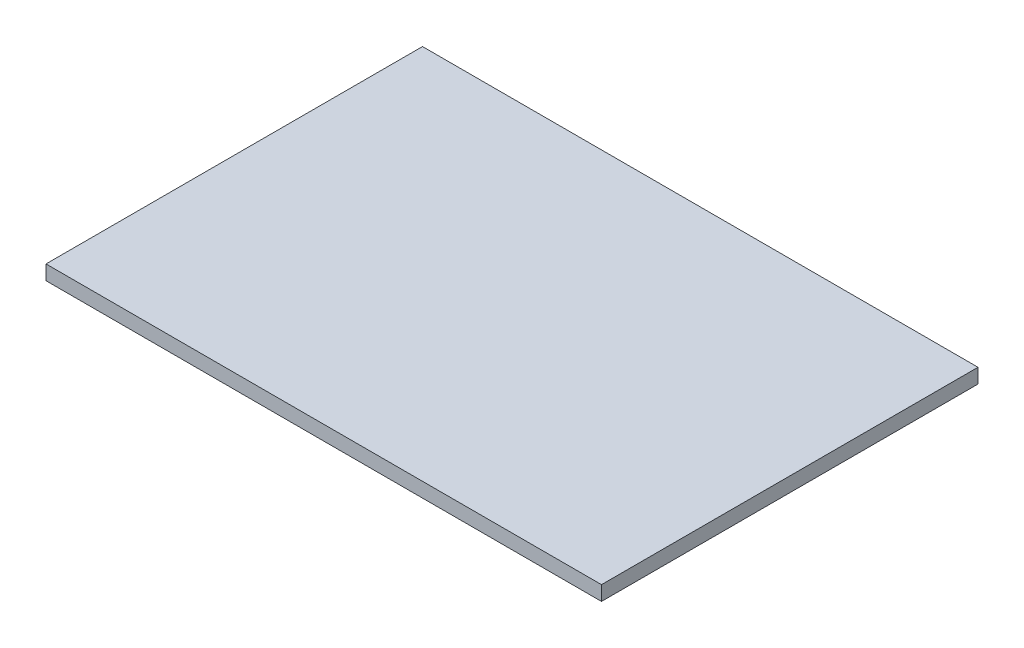
SolidWorks part; units mm, degrees
ref_plane "Front Plane" through (0, 0, 0) normal (0, 0, 1) x (1, 0, 0)
ref_plane "Top Plane" through (0, 0, 0) normal (0, 1, 0) x (1, 0, 0)
ref_plane "Right Plane" through (0, 0, 0) normal (1, 0, 0) x (0, 0, -1)
sketch "Sketch1" plane through (0, 0, 0) normal (0, 1, 0) x (1, 0, 0)
  line L1 (-45, 30.5) -> (45, 30.5)
  line L2 (-45, 30.5) -> (-45, -30.5)
  line L3 (-45, -30.5) -> (45, -30.5)
  line L4 (45, 30.5) -> (45, -30.5)
  line L5 (-45, 30.5) -> (45, -30.5) construction
  line L6 (-45, -30.5) -> (45, 30.5) construction
  point P0 (0, 0)
  dimension "D1" = 61
  dimension "D2" = 90
extrude "Boss-Extrude1" add sketch "Sketch1" along normal mid plane 2.36
sketch "Sketch2" plane through (0, -1.18, 0) normal (0, -1, 0) x (1, 0, 0)
  line L0 (-9, -1.05) -> (-9, -11.25) construction
  line L1 (45, 30.5) -> (-45, 30.5)
  line L2 (45, 30.5) -> (45, -30.5)
  line L3 (45, -30.5) -> (-45, -30.5)
  line L4 (-45, 30.5) -> (-45, -30.5)
  line L5 (-9, 0.05) -> (-32, 0.05)
  line L6 (-9, 0.05) -> (-9, 11.25)
  line L7 (-9, 11.25) -> (-32, 11.25)
  line L8 (-32, 0.05) -> (-32, 11.25)
  line L9 (-32, -0.05) -> (-9, -0.05)
  line L10 (-32, -0.05) -> (-32, -11.25)
  line L11 (-32, -11.25) -> (-9, -11.25)
  line L12 (-9, -0.05) -> (-9, -11.25)
  line L13 (11.4572, 30.5) -> (11.4572, -30.5)
  line L134 (11.4572, 38.6) -> (11.4572, -38.6) construction
  line L135 (-43.5487, 0.655) -> (-43.5487, 0.305)
  line L136 (-43.5487, 3.195) -> (-43.1487, 3.195)
  line L137 (-0.0946, -23.8068) -> (6.2919, -23.8068)
  line L138 (-0.0946, -23.8068) -> (-0.0946, -30.1932)
  line L139 (-0.0946, -30.1932) -> (6.2919, -30.1932)
  line L140 (6.2919, -23.8068) -> (6.2919, -30.1932)
  line L141 (-43.5487, 3.195) -> (-43.5487, 2.845)
  line L142 (-43.5487, 2.845) -> (-43.1487, 2.845)
  line L143 (-43.1487, 3.195) -> (-43.1487, 2.845)
  line L144 (-43.5487, 0.655) -> (-43.1487, 0.655)
  line L145 (-43.1487, 0.655) -> (-43.1487, 0.305)
  line L146 (-43.5487, 0.305) -> (-43.1487, 0.305)
  line L147 (-43.5487, -1.885) -> (-43.5487, -2.235)
  line L148 (-43.5487, -1.885) -> (-43.1487, -1.885)
  line L149 (-43.1487, -1.885) -> (-43.1487, -2.235)
  line L150 (-43.5487, -2.235) -> (-43.1487, -2.235)
  line L151 (-43.5487, -4.425) -> (-43.5487, -4.775)
  line L152 (-43.5487, -4.425) -> (-43.1487, -4.425)
  line L153 (-43.1487, -4.425) -> (-43.1487, -4.775)
  line L154 (-43.5487, -4.775) -> (-43.1487, -4.775)
  line L155 (-43.5487, -6.965) -> (-43.5487, -7.315)
  line L156 (-43.5487, -6.965) -> (-43.1487, -6.965)
  line L157 (-43.1487, -6.965) -> (-43.1487, -7.315)
  line L158 (-43.5487, -7.315) -> (-43.1487, -7.315)
  line L159 (-43.5487, -9.505) -> (-43.5487, -9.855)
  line L160 (-43.5487, -9.505) -> (-43.1487, -9.505)
  line L161 (-43.1487, -9.505) -> (-43.1487, -9.855)
  line L162 (-43.5487, -9.855) -> (-43.1487, -9.855)
  line L163 (-43.5487, 3.195) -> (-43.5487, 0.655) construction
  line L164 (-6.85, 13.02) -> (-6.85, 12.38)
  line L165 (-6.85, 15.56) -> (-6.21, 15.56)
  line L166 (-6.85, 15.56) -> (-6.85, 14.92)
  line L167 (-6.85, 14.92) -> (-6.21, 14.92)
  line L168 (-6.21, 15.56) -> (-6.21, 14.92)
  line L169 (-6.85, 13.02) -> (-6.21, 13.02)
  line L170 (-6.21, 13.02) -> (-6.21, 12.38)
  line L171 (-6.85, 12.38) -> (-6.21, 12.38)
  line L172 (-6.85, 10.48) -> (-6.85, 9.84)
  line L173 (-6.85, 10.48) -> (-6.21, 10.48)
  line L174 (-6.21, 10.48) -> (-6.21, 9.84)
  line L175 (-6.85, 9.84) -> (-6.21, 9.84)
  line L176 (-6.85, 7.94) -> (-6.85, 7.3)
  line L177 (-6.85, 7.94) -> (-6.21, 7.94)
  line L178 (-6.21, 7.94) -> (-6.21, 7.3)
  line L179 (-6.85, 7.3) -> (-6.21, 7.3)
  line L180 (-6.85, 5.4) -> (-6.85, 4.76)
  line L181 (-6.85, 5.4) -> (-6.21, 5.4)
  line L182 (-6.21, 5.4) -> (-6.21, 4.76)
  line L183 (-6.85, 4.76) -> (-6.21, 4.76)
  line L184 (-6.85, 2.86) -> (-6.85, 2.22)
  line L185 (-6.85, 2.86) -> (-6.21, 2.86)
  line L186 (-6.21, 2.86) -> (-6.21, 2.22)
  line L187 (-6.85, 2.22) -> (-6.21, 2.22)
  line L188 (-6.85, 0.32) -> (-6.85, -0.32)
  line L189 (-6.85, 0.32) -> (-6.21, 0.32)
  line L190 (-6.21, 0.32) -> (-6.21, -0.32)
  line L191 (-6.85, -0.32) -> (-6.21, -0.32)
  line L192 (-6.85, -2.22) -> (-6.85, -2.86)
  line L193 (-6.85, -2.22) -> (-6.21, -2.22)
  line L194 (-6.21, -2.22) -> (-6.21, -2.86)
  line L195 (-6.85, -2.86) -> (-6.21, -2.86)
  line L196 (-6.85, -4.76) -> (-6.85, -5.4)
  line L197 (-6.85, -4.76) -> (-6.21, -4.76)
  line L198 (-6.21, -4.76) -> (-6.21, -5.4)
  line L199 (-6.85, -5.4) -> (-6.21, -5.4)
  line L200 (-6.85, -7.3) -> (-6.85, -7.94)
  line L201 (-6.85, -7.3) -> (-6.21, -7.3)
  line L202 (-6.21, -7.3) -> (-6.21, -7.94)
  line L203 (-6.85, -7.94) -> (-6.21, -7.94)
  line L204 (-6.85, -9.84) -> (-6.85, -10.48)
  line L205 (-6.85, -9.84) -> (-6.21, -9.84)
  line L206 (-6.21, -9.84) -> (-6.21, -10.48)
  line L207 (-6.85, -10.48) -> (-6.21, -10.48)
  line L208 (-6.85, -12.38) -> (-6.85, -13.02)
  line L209 (-6.85, -12.38) -> (-6.21, -12.38)
  line L210 (-6.21, -12.38) -> (-6.21, -13.02)
  line L211 (-6.85, -13.02) -> (-6.21, -13.02)
  line L212 (-6.85, -14.92) -> (-6.85, -15.56)
  line L213 (-6.85, -14.92) -> (-6.21, -14.92)
  line L214 (-6.21, -14.92) -> (-6.21, -15.56)
  line L215 (-6.85, -15.56) -> (-6.21, -15.56)
  line L216 (-6.85, -17.46) -> (-6.85, -18.1)
  line L217 (-6.85, -17.46) -> (-6.21, -17.46)
  line L218 (-6.21, -17.46) -> (-6.21, -18.1)
  line L219 (-6.85, -18.1) -> (-6.21, -18.1)
  line L220 (-6.85, -20) -> (-6.85, -20.64)
  line L221 (-6.85, -20) -> (-6.21, -20)
  line L222 (-6.21, -20) -> (-6.21, -20.64)
  line L223 (-6.85, -20.64) -> (-6.21, -20.64)
  line L224 (-6.85, 15.56) -> (-6.85, 13.02) construction
  line L225 (-34.79, 7.94) -> (-34.79, 7.3)
  line L226 (-2.4189, 29.58) -> (-1.6269, 29.58)
  line L227 (-2.4189, 29.58) -> (-2.4189, 28.5)
  line L228 (-2.4189, 28.5) -> (-1.6269, 28.5)
  line L229 (-1.6269, 29.58) -> (-1.6269, 28.5)
  line L230 (-2.4189, 23.82) -> (-1.6269, 23.82)
  line L231 (-2.4189, 23.82) -> (-2.4189, 22.74)
  line L232 (-2.4189, 22.74) -> (-1.6269, 22.74)
  line L233 (-1.6269, 23.82) -> (-1.6269, 22.74)
  line L234 (7.8241, 29.58) -> (8.6161, 29.58)
  line L235 (7.8241, 29.58) -> (7.8241, 28.5)
  line L236 (7.8241, 28.5) -> (8.6161, 28.5)
  line L237 (8.6161, 29.58) -> (8.6161, 28.5)
  line L238 (7.8241, 23.82) -> (8.6161, 23.82)
  line L239 (7.8241, 23.82) -> (7.8241, 22.74)
  line L240 (7.8241, 22.74) -> (8.6161, 22.74)
  line L241 (8.6161, 23.82) -> (8.6161, 22.74)
  line L242 (-0.2134, 29.472) -> (6.4106, 29.472)
  line L243 (-0.2134, 29.472) -> (-0.2134, 22.848)
  line L244 (-0.2134, 22.848) -> (6.4106, 22.848)
  line L245 (6.4106, 29.472) -> (6.4106, 22.848)
  line L246 (-34.79, 10.48) -> (-34.15, 10.48)
  line L247 (-34.79, 10.48) -> (-34.79, 9.84)
  line L248 (-34.79, 9.84) -> (-34.15, 9.84)
  line L249 (-34.15, 10.48) -> (-34.15, 9.84)
  line L250 (-34.79, 7.94) -> (-34.15, 7.94)
  line L251 (-34.15, 7.94) -> (-34.15, 7.3)
  line L252 (-34.79, 7.3) -> (-34.15, 7.3)
  line L253 (-34.79, 5.4) -> (-34.79, 4.76)
  line L254 (-34.79, 5.4) -> (-34.15, 5.4)
  line L255 (-34.15, 5.4) -> (-34.15, 4.76)
  line L256 (-34.79, 4.76) -> (-34.15, 4.76)
  line L257 (-34.79, 2.86) -> (-34.79, 2.22)
  line L258 (-34.79, 2.86) -> (-34.15, 2.86)
  line L259 (-34.15, 2.86) -> (-34.15, 2.22)
  line L260 (-34.79, 2.22) -> (-34.15, 2.22)
  line L261 (-34.79, 0.32) -> (-34.79, -0.32)
  line L262 (-34.79, 0.32) -> (-34.15, 0.32)
  line L263 (-34.15, 0.32) -> (-34.15, -0.32)
  line L264 (-34.79, -0.32) -> (-34.15, -0.32)
  line L265 (-34.79, -2.22) -> (-34.79, -2.86)
  line L266 (-34.79, -2.22) -> (-34.15, -2.22)
  line L267 (-34.15, -2.22) -> (-34.15, -2.86)
  line L268 (-34.79, -2.86) -> (-34.15, -2.86)
  line L269 (-34.79, -4.76) -> (-34.79, -5.4)
  line L270 (-34.79, -4.76) -> (-34.15, -4.76)
  line L271 (-34.15, -4.76) -> (-34.15, -5.4)
  line L272 (-34.79, -5.4) -> (-34.15, -5.4)
  line L273 (-34.79, -7.3) -> (-34.79, -7.94)
  line L274 (-34.79, -7.3) -> (-34.15, -7.3)
  line L275 (-34.15, -7.3) -> (-34.15, -7.94)
  line L276 (-34.79, -7.94) -> (-34.15, -7.94)
  line L277 (-34.79, -9.84) -> (-34.79, -10.48)
  line L278 (-34.79, -9.84) -> (-34.15, -9.84)
  line L279 (-34.15, -9.84) -> (-34.15, -10.48)
  line L280 (-34.79, -10.48) -> (-34.15, -10.48)
  line L281 (-34.79, 10.48) -> (-34.79, 7.94) construction
  line L283 (-24.25, -28.34) -> (-16.75, -28.34)
  line L284 (-24.25, -28.34) -> (-24.25, -33.04)
  line L285 (-36.25, 26.51) -> (-4.75, 26.51)
  line L286 (-36.25, 26.51) -> (-36.25, -31.59)
  line L287 (-36.25, -31.59) -> (-4.75, -31.59)
  line L288 (-4.75, 26.51) -> (-4.75, -31.59)
  line L289 (-24.25, -33.04) -> (-16.75, -33.04)
  line L290 (-16.75, -28.34) -> (-16.75, -33.04)
  circle A0 centre (-13, 5.65) radius 1.5
  circle A1 centre (-28, 5.65) radius 1.5
  circle A2 centre (-28, -5.65) radius 1.5
  circle A3 centre (-13, -5.65) radius 1.5
  circle A4 centre (6.9572, 7.55) radius 1.5
  circle A5 centre (6.9572, -7.45) radius 1.5
  circle A9 centre (42.5, 12.15) radius 1.2294
  circle A10 centre (42.5, -12.05) radius 1.2294
  circle A11 centre (21.4572, 0) radius 1.2294
  circle A12 centre (0.5986, -24.5) radius 0.3354
  circle A13 centre (5.5986, -24.5) radius 0.3354
  circle A14 centre (5.5986, -29.5) radius 0.3354
  circle A15 centre (0.5986, -29.5) radius 0.3354
  circle A16 centre (0.5986, -27) radius 0.3354
  circle A17 centre (5.5986, -27) radius 0.3354
  dimension "D1" = 2.54
  dimension "D2" = 2.54
  dimension "D3" = 2.54
